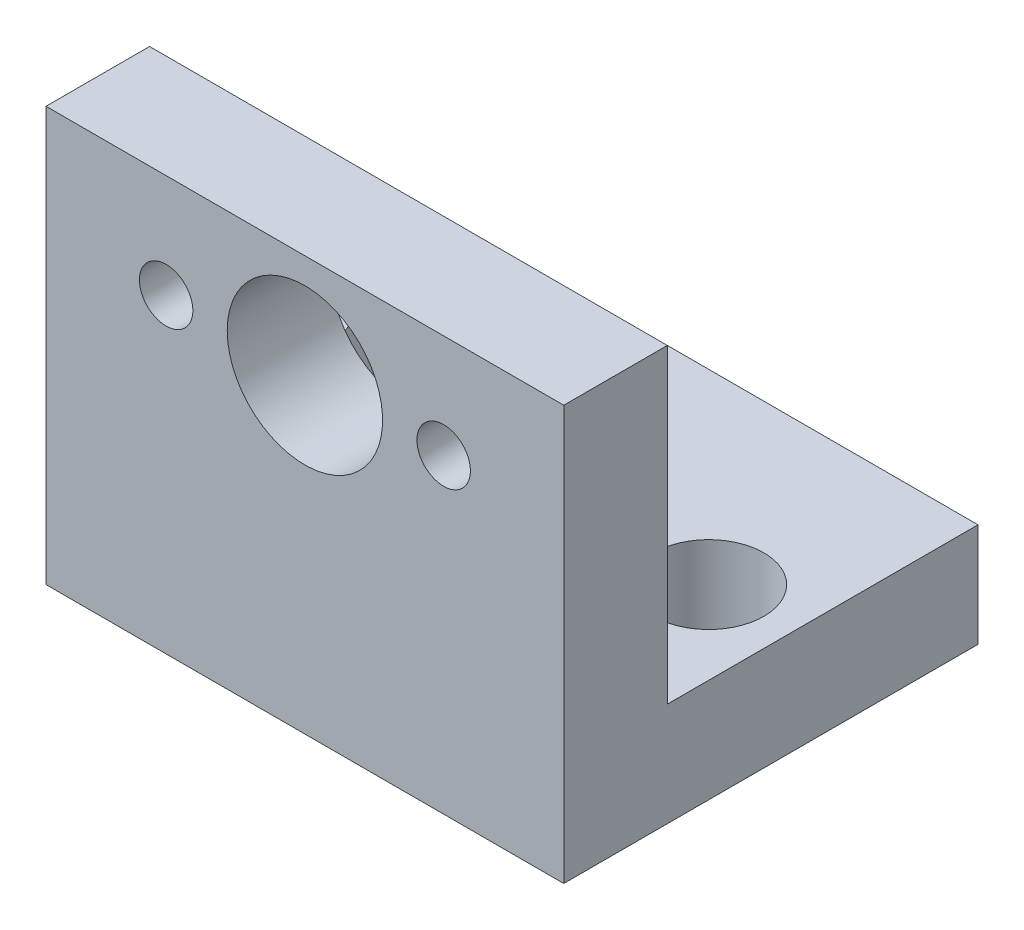
SolidWorks part; units mm, degrees
material "1023 Carbon Steel Sheet (SS)"
ref_plane "Front Plane" through (0, 0, 0) normal (0, 0, 1) x (1, 0, 0)
ref_plane "Top Plane" through (0, 0, 0) normal (0, 1, 0) x (1, 0, 0)
ref_plane "Right Plane" through (0, 0, 0) normal (1, 0, 0) x (0, 0, -1)
sketch "Sketch2" plane through (0, 0, 0) normal (1, 0, 0) x (0, 0, -1)
  line L0 (0, 0) -> (25.4, 0)
  line L1 (25.4, 0) -> (25.4, 6.35)
  line L2 (25.4, 6.35) -> (6.35, 6.35)
  line L3 (6.35, 6.35) -> (6.35, 25.4)
  line L4 (6.35, 25.4) -> (0, 25.4)
  line L5 (0, 25.4) -> (0, 0)
  dimension "D1" = 6.35
  dimension "D2" = 6.35
  dimension "D3" = 25.4
  dimension "D4" = 25.4
extrude "Boss-Extrude1" add sketch "Sketch2" along normal blind 31.75
sketch "Sketch3" plane through (0, 0, -6.35) normal (0, 0, -1) x (-1, 0, 0)
  line L1 (0, 6.35) -> (0, 25.4) construction
  line L2 (-31.75, 0) -> (0, 0) construction
  circle A0 centre (-15.875, 19.05) radius 4.7625
  circle A1 centre (-7.366, 19.05) radius 1.6383
  circle A2 centre (-24.384, 19.05) radius 1.6383
  dimension "D1" = 8.509
  dimension "D2" = 8.509
  dimension "D3" = 3.2766
  dimension "D4" = 3.2766
  dimension "D6" = 9.525
  dimension "D5" = 19.05
  dimension "D7" = 15.875
extrude "Cut-Extrude1" cut sketch "Sketch3" against normal through all
sketch "Sketch4" plane through (0, 6.35, 0) normal (0, 1, 0) x (1, 0, 0)
  line L0 (0, 25.4) -> (0, 6.35) construction
  line L1 (31.75, 25.4) -> (31.75, 6.35) construction
  line L2 (31.75, 25.4) -> (0, 25.4) construction
  circle A1 centre (5.08, 17.78) radius 3.3782
  circle A2 centre (26.67, 13.97) radius 3.3782
  dimension "D1" = 5.08
  dimension "D3" = 5.08
  dimension "D4" = 6.7564
  dimension "D2" = 6.7564
  dimension "D5" = 7.62
  dimension "D6" = 11.43
extrude "Cut-Extrude2" cut sketch "Sketch4" against normal through all
